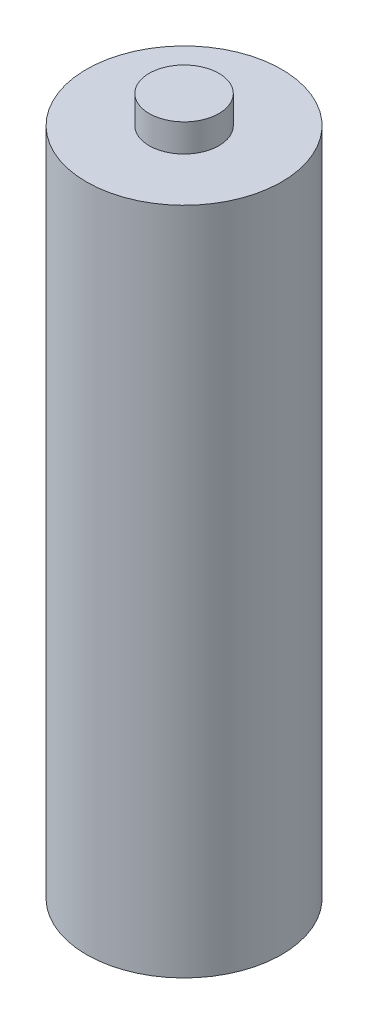
SolidWorks part; units mm, degrees
ref_plane "前视基准面" through (0, 0, 0) normal (0, 0, 1) x (1, 0, 0)
ref_plane "上视基准面" through (0, 0, 0) normal (0, 1, 0) x (1, 0, 0)
ref_plane "右视基准面" through (0, 0, 0) normal (1, 0, 0) x (0, 0, -1)
other "Configuration Table"
sketch "草图1" plane through (0, 0, 0) normal (0, 1, 0) x (1, 0, 0)
  circle A0 centre (0, 0) radius 7
  circle A1 centre (0, 0) radius 2.5
  dimension "D1" = 14
  dimension "D2" = 5
extrude "凸台-拉伸1" add sketch "草图1" along normal blind 50 contours A1
extrude "凸台-拉伸2" add sketch "草图1<3>" along normal blind 48 contours A0
sketch "草图1<3>" plane through (0, 0, 0) normal (0, 1, 0) x (1, 0, 0) same geometry as "草图1"
